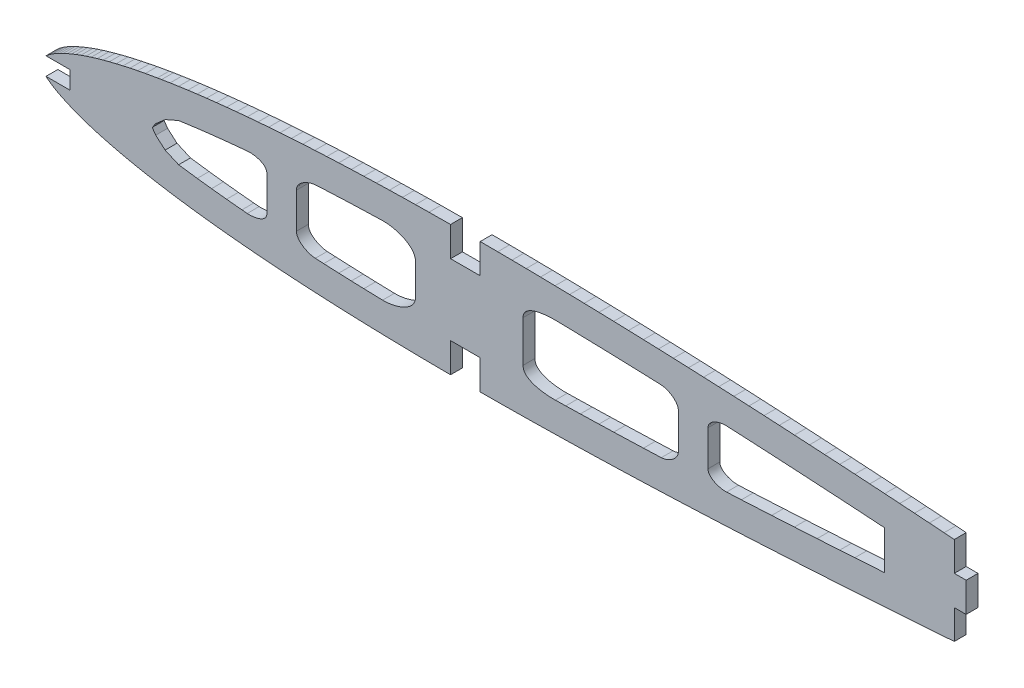
SolidWorks part; units mm, degrees
ref_plane "前视基准面" through (0, 0, 0) normal (0, 0, 1) x (1, 0, 0)
ref_plane "上视基准面" through (0, 0, 0) normal (0, 1, 0) x (1, 0, 0)
ref_plane "右视基准面" through (0, 0, 0) normal (1, 0, 0) x (0, 0, -1)
sketch "Model" plane through (0, 0, 0) normal (0, 0, 1) x (1, 0, 0)
  line L0 (365.1559, -97.3973) -> (369.2164, -97.3973)
  line L1 (369.2164, -97.3973) -> (369.2164, -100.3973)
  line L2 (369.2164, -100.3973) -> (365.1559, -100.3973)
  line L3 (438.4064, -87.9083) -> (438.4104, -92.9083)
  line L4 (438.4104, -92.9083) -> (433.4104, -92.9143)
  line L5 (433.4104, -92.9143) -> (433.4064, -87.9143)
  line L6 (438.4064, -109.8863) -> (438.4124, -104.8863)
  line L7 (438.4124, -104.8863) -> (433.4124, -104.8803)
  line L8 (433.4124, -104.8803) -> (433.4064, -109.8803)
  line L9 (518.3903, -91.4457) -> (516.6664, -91.3183)
  line L10 (516.6664, -91.3183) -> (514.1714, -91.1393)
  line L11 (514.1714, -91.1393) -> (511.6764, -90.9633)
  line L12 (511.6764, -90.9633) -> (509.1804, -90.7903)
  line L13 (509.1804, -90.7903) -> (506.6554, -90.6183)
  line L14 (506.6554, -90.6183) -> (504.1314, -90.4503)
  line L15 (504.1314, -90.4503) -> (501.6054, -90.2873)
  line L16 (501.6054, -90.2873) -> (499.0594, -90.1283)
  line L17 (499.0594, -90.1283) -> (496.5144, -89.9743)
  line L18 (496.5144, -89.9743) -> (493.9684, -89.8233)
  line L19 (493.9684, -89.8233) -> (491.4134, -89.6743)
  line L20 (491.4134, -89.6743) -> (488.8584, -89.5283)
  line L21 (488.8584, -89.5283) -> (486.3034, -89.3863)
  line L22 (486.3034, -89.3863) -> (483.7484, -89.2513)
  line L23 (483.7484, -89.2513) -> (481.1944, -89.1213)
  line L24 (481.1944, -89.1213) -> (478.6384, -88.9983)
  line L25 (478.6384, -88.9983) -> (476.0924, -88.8813)
  line L26 (476.0924, -88.8813) -> (473.5474, -88.7693)
  line L27 (473.5474, -88.7693) -> (471.0014, -88.6633)
  line L28 (471.0014, -88.6633) -> (468.4764, -88.5643)
  line L29 (468.4764, -88.5643) -> (465.9524, -88.4703)
  line L30 (465.9524, -88.4703) -> (463.4264, -88.3833)
  line L31 (463.4264, -88.3833) -> (460.9314, -88.3033)
  line L32 (460.9314, -88.3033) -> (458.4364, -88.2303)
  line L33 (458.4364, -88.2303) -> (455.9404, -88.1633)
  line L34 (455.9404, -88.1633) -> (453.4854, -88.1043)
  line L35 (453.4854, -88.1043) -> (451.0314, -88.0523)
  line L36 (451.0314, -88.0523) -> (448.5764, -88.0073)
  line L37 (448.5764, -88.0073) -> (446.1704, -87.9703)
  line L38 (446.1704, -87.9703) -> (443.7664, -87.9423)
  line L39 (443.7664, -87.9423) -> (441.3604, -87.9213)
  line L40 (441.3604, -87.9213) -> (438.4064, -87.9083)
  line L41 (383.9404, -91.2373) -> (379.0174, -92.1113)
  line L42 (387.5324, -95.6683) -> (390.6644, -95.2413)
  line L43 (390.6644, -95.2413) -> (393.0784, -94.9513)
  line L44 (393.0784, -94.9513) -> (395.6144, -94.6733)
  line L45 (395.6144, -94.6733) -> (398.2099, -94.4193)
  line L46 (398.2099, -94.4193) -> (399.256, -94.3267)
  line L47 (410.7501, -93.5242) -> (412.0079, -93.4582)
  line L48 (412.0079, -93.4582) -> (414.9885, -93.3234)
  line L49 (414.9885, -93.3234) -> (416.6574, -93.2563)
  line L50 (416.6574, -93.2563) -> (418.7714, -93.1823)
  line L51 (418.7714, -93.1823) -> (421.9864, -93.0883)
  line L52 (421.9343, -104.7047) -> (418.7714, -104.6123)
  line L53 (418.7714, -104.6123) -> (416.6574, -104.5383)
  line L54 (416.6574, -104.5383) -> (414.5434, -104.4533)
  line L55 (414.5434, -104.4533) -> (412.0079, -104.3363)
  line L56 (412.0079, -104.3363) -> (410.5909, -104.2619)
  line L57 (399.1076, -103.4547) -> (398.2099, -103.3753)
  line L58 (398.2099, -103.3753) -> (395.6144, -103.1213)
  line L59 (395.6144, -103.1213) -> (393.0784, -102.8433)
  line L60 (393.0784, -102.8433) -> (390.6644, -102.5533)
  line L61 (390.6644, -102.5533) -> (387.5324, -102.1263)
  line L62 (451.3201, -93.0601) -> (452.8362, -93.0905)
  line L63 (452.8362, -93.0905) -> (455.2997, -93.1479)
  line L64 (455.2997, -93.1479) -> (458.4364, -93.2303)
  line L65 (458.4364, -93.2303) -> (460.9314, -93.3033)
  line L66 (460.9314, -93.3033) -> (465.9524, -93.4703)
  line L67 (465.9524, -93.4703) -> (468.8582, -93.5804)
  line L68 (479.9184, -94.063) -> (482.4714, -94.1863)
  line L69 (482.4714, -94.1863) -> (487.5809, -94.4573)
  line L70 (487.5809, -94.4573) -> (491.4134, -94.6743)
  line L71 (491.4134, -94.6743) -> (495.2414, -94.8988)
  line L72 (495.2414, -94.8988) -> (499.0594, -95.1283)
  line L73 (499.0594, -95.1283) -> (501.6054, -95.2873)
  line L74 (501.6054, -95.2873) -> (506.6554, -95.6183)
  line L75 (506.6554, -102.1763) -> (501.6054, -102.5073)
  line L76 (501.6054, -102.5073) -> (499.0594, -102.6663)
  line L77 (499.0594, -102.6663) -> (495.2414, -102.8958)
  line L78 (495.2414, -102.8958) -> (491.4134, -103.1203)
  line L79 (491.4134, -103.1203) -> (487.5809, -103.3373)
  line L80 (487.5809, -103.3373) -> (482.4714, -103.6083)
  line L81 (482.4714, -103.6083) -> (479.9656, -103.7292)
  line L82 (468.9559, -104.2104) -> (465.9524, -104.3243)
  line L83 (465.9524, -104.3243) -> (460.9314, -104.4913)
  line L84 (460.9314, -104.4913) -> (458.4364, -104.5643)
  line L85 (458.4364, -104.5643) -> (455.2997, -104.6467)
  line L86 (455.2997, -104.6467) -> (452.8362, -104.704)
  line L87 (452.8362, -104.704) -> (451.0861, -104.7391)
  line L88 (387.5324, -95.6683) -> (385.2532, -96.6702)
  line L89 (385.2532, -96.6702) -> (383.6712, -98.0522)
  line L90 (383.6712, -98.0522) -> (383.078, -98.8973)
  line L91 (387.5324, -102.1263) -> (385.2532, -101.1243)
  line L92 (385.2532, -101.1243) -> (383.6712, -99.7423)
  line L93 (383.6712, -99.7423) -> (383.078, -98.8973)
  line L94 (427.4864, -96.2466) -> (427.4864, -101.548)
  line L95 (445.635, -95.4141) -> (445.635, -102.3805)
  line L96 (407.4071, -95.8973) -> (407.4071, -101.8973)
  line L97 (402.4071, -101.8973) -> (402.4071, -95.8973)
  line L98 (476.8379, -95.8973) -> (476.8379, -101.8973)
  line L99 (471.8379, -101.8973) -> (471.8379, -95.8973)
  line L100 (520.3903, -98.8973) -> (520.3903, -96.3973)
  line L101 (520.3903, -98.8973) -> (520.3903, -101.3973)
  line L102 (520.3903, -96.3973) -> (518.3903, -96.3973)
  line L103 (520.3903, -101.3973) -> (518.3903, -101.3973)
  line L104 (518.3903, -96.3973) -> (518.3903, -91.444)
  line L105 (518.3903, -101.3973) -> (518.3903, -106.3499)
  line L106 (506.6554, -95.6183) -> (506.6554, -102.1763)
  line L107 (433.4064, -87.9143) -> (429.7654, -87.9423)
  line L108 (429.7654, -87.9423) -> (427.4864, -87.9723)
  line L109 (427.4864, -87.9723) -> (425.2864, -88.0113)
  line L110 (425.2864, -88.0113) -> (423.0864, -88.0593)
  line L111 (423.0864, -88.0593) -> (420.8864, -88.1173)
  line L112 (420.8864, -88.1173) -> (418.7714, -88.1823)
  line L113 (418.7714, -88.1823) -> (416.6574, -88.2563)
  line L114 (416.6574, -88.2563) -> (414.5434, -88.3413)
  line L115 (414.5434, -88.3413) -> (412.5224, -88.4323)
  line L116 (412.5224, -88.4323) -> (410.5024, -88.5343)
  line L117 (410.5024, -88.5343) -> (408.4824, -88.6463)
  line L118 (408.4824, -88.6463) -> (406.5644, -88.7643)
  line L119 (406.5644, -88.7643) -> (404.6474, -88.8943)
  line L120 (404.6474, -88.8943) -> (402.7304, -89.0353)
  line L121 (402.7304, -89.0353) -> (400.9214, -89.1793)
  line L122 (400.9214, -89.1793) -> (399.1134, -89.3353)
  line L123 (399.1134, -89.3353) -> (397.3064, -89.5033)
  line L124 (397.3064, -89.5033) -> (395.6144, -89.6733)
  line L125 (395.6144, -89.6733) -> (393.9234, -89.8543)
  line L126 (393.9234, -89.8543) -> (392.2334, -90.0483)
  line L127 (392.2334, -90.0483) -> (390.6644, -90.2413)
  line L128 (390.6644, -90.2413) -> (389.0974, -90.4483)
  line L129 (389.0974, -90.4483) -> (387.5324, -90.6683)
  line L130 (387.5324, -90.6683) -> (386.0934, -90.8853)
  line L131 (386.0934, -90.8853) -> (384.6574, -91.1153)
  line L132 (384.6574, -91.1153) -> (383.2234, -91.3593)
  line L133 (383.2234, -91.3593) -> (381.9184, -91.5963)
  line L134 (381.9184, -91.5963) -> (380.6174, -91.8473)
  line L135 (380.6174, -91.8473) -> (379.3184, -92.1143)
  line L136 (379.3184, -92.1143) -> (378.1544, -92.3693)
  line L137 (378.1544, -92.3693) -> (376.9934, -92.6403)
  line L138 (376.9934, -92.6403) -> (375.8364, -92.9273)
  line L139 (375.8364, -92.9273) -> (374.8164, -93.1963)
  line L140 (374.8164, -93.1963) -> (373.8004, -93.4803)
  line L141 (373.8004, -93.4803) -> (372.7894, -93.7843)
  line L142 (372.7894, -93.7843) -> (371.9164, -94.0643)
  line L143 (371.9164, -94.0643) -> (371.0504, -94.3633)
  line L144 (371.0504, -94.3633) -> (370.1914, -94.6823)
  line L145 (370.1914, -94.6823) -> (369.4714, -94.9713)
  line L146 (369.4714, -94.9713) -> (368.7584, -95.2773)
  line L147 (368.7584, -95.2773) -> (368.0524, -95.6003)
  line L148 (368.0524, -95.6003) -> (367.4844, -95.8783)
  line L149 (367.4844, -95.8783) -> (366.9254, -96.1743)
  line L150 (366.9254, -96.1743) -> (366.3794, -96.4943)
  line L151 (366.3794, -96.4943) -> (365.9634, -96.7673)
  line L152 (365.9634, -96.7673) -> (365.5614, -97.0603)
  line L153 (365.5614, -97.0603) -> (365.1784, -97.3763)
  line L154 (365.1784, -97.3763) -> (365.1559, -97.3973)
  line L155 (438.4064, -109.8863) -> (441.3604, -109.8723)
  line L156 (441.3604, -109.8723) -> (443.7664, -109.8523)
  line L157 (443.7664, -109.8523) -> (446.1704, -109.8233)
  line L158 (446.1704, -109.8233) -> (448.5764, -109.7873)
  line L159 (448.5764, -109.7873) -> (451.0314, -109.7423)
  line L160 (451.0314, -109.7423) -> (453.4854, -109.6903)
  line L161 (453.4854, -109.6903) -> (455.9404, -109.6313)
  line L162 (455.9404, -109.6313) -> (458.4364, -109.5643)
  line L163 (458.4364, -109.5643) -> (460.9314, -109.4913)
  line L164 (460.9314, -109.4913) -> (463.4264, -109.4113)
  line L165 (463.4264, -109.4113) -> (465.9524, -109.3233)
  line L166 (465.9524, -109.3233) -> (468.4764, -109.2303)
  line L167 (468.4764, -109.2303) -> (471.0014, -109.1303)
  line L168 (471.0014, -109.1303) -> (473.5474, -109.0243)
  line L169 (473.5474, -109.0243) -> (476.0924, -108.9133)
  line L170 (476.0924, -108.9133) -> (478.6384, -108.7963)
  line L171 (478.6384, -108.7963) -> (481.1944, -108.6723)
  line L172 (481.1944, -108.6723) -> (483.7484, -108.5433)
  line L173 (483.7484, -108.5433) -> (486.3034, -108.4073)
  line L174 (486.3034, -108.4073) -> (488.8584, -108.2663)
  line L175 (488.8584, -108.2663) -> (491.4134, -108.1203)
  line L176 (491.4134, -108.1203) -> (493.9684, -107.9703)
  line L177 (493.9684, -107.9703) -> (496.5144, -107.8193)
  line L178 (496.5144, -107.8193) -> (499.0594, -107.6653)
  line L179 (499.0594, -107.6653) -> (501.6054, -107.5063)
  line L180 (501.6054, -107.5063) -> (504.1314, -107.3433)
  line L181 (504.1314, -107.3433) -> (506.6554, -107.1753)
  line L182 (506.6554, -107.1753) -> (509.1804, -107.0033)
  line L183 (509.1804, -107.0033) -> (511.6764, -106.8313)
  line L184 (511.6764, -106.8313) -> (514.1714, -106.6553)
  line L185 (514.1714, -106.6553) -> (516.6664, -106.4763)
  line L186 (516.6664, -106.4763) -> (518.3903, -106.3499)
  line L187 (365.1559, -100.3973) -> (365.1784, -100.4183)
  line L188 (365.1784, -100.4183) -> (365.5614, -100.7343)
  line L189 (365.5614, -100.7343) -> (365.9634, -101.0273)
  line L190 (365.9634, -101.0273) -> (366.3794, -101.2993)
  line L191 (366.3794, -101.2993) -> (366.9254, -101.6203)
  line L192 (366.9254, -101.6203) -> (367.4844, -101.9153)
  line L193 (367.4844, -101.9153) -> (368.0524, -102.1933)
  line L194 (368.0524, -102.1933) -> (368.7584, -102.5173)
  line L195 (368.7584, -102.5173) -> (369.4714, -102.8233)
  line L196 (369.4714, -102.8233) -> (370.1914, -103.1113)
  line L197 (370.1914, -103.1113) -> (371.0504, -103.4313)
  line L198 (371.0504, -103.4313) -> (371.9164, -103.7293)
  line L199 (371.9164, -103.7293) -> (372.7894, -104.0103)
  line L200 (372.7894, -104.0103) -> (373.8004, -104.3133)
  line L201 (373.8004, -104.3133) -> (374.8164, -104.5983)
  line L202 (374.8164, -104.5983) -> (375.8364, -104.8673)
  line L203 (375.8364, -104.8673) -> (376.9934, -105.1543)
  line L204 (376.9934, -105.1543) -> (378.1544, -105.4253)
  line L205 (378.1544, -105.4253) -> (379.3184, -105.6803)
  line L206 (379.3184, -105.6803) -> (380.6174, -105.9473)
  line L207 (380.6174, -105.9473) -> (381.9184, -106.1983)
  line L208 (381.9184, -106.1983) -> (383.2234, -106.4343)
  line L209 (383.2234, -106.4343) -> (384.6574, -106.6793)
  line L210 (384.6574, -106.6793) -> (386.0934, -106.9093)
  line L211 (386.0934, -106.9093) -> (387.5324, -107.1253)
  line L212 (387.5324, -107.1253) -> (389.0974, -107.3463)
  line L213 (389.0974, -107.3463) -> (390.6644, -107.5523)
  line L214 (390.6644, -107.5523) -> (392.2334, -107.7463)
  line L215 (392.2334, -107.7463) -> (393.9234, -107.9403)
  line L216 (393.9234, -107.9403) -> (395.6144, -108.1213)
  line L217 (395.6144, -108.1213) -> (397.3064, -108.2903)
  line L218 (397.3064, -108.2903) -> (399.1134, -108.4583)
  line L219 (399.1134, -108.4583) -> (400.9214, -108.6143)
  line L220 (400.9214, -108.6143) -> (402.7304, -108.7593)
  line L221 (402.7304, -108.7593) -> (404.6474, -108.9003)
  line L222 (404.6474, -108.9003) -> (406.5644, -109.0293)
  line L223 (406.5644, -109.0293) -> (408.4824, -109.1473)
  line L224 (408.4824, -109.1473) -> (410.5024, -109.2603)
  line L225 (410.5024, -109.2603) -> (412.5224, -109.3613)
  line L226 (412.5224, -109.3613) -> (414.5434, -109.4523)
  line L227 (414.5434, -109.4523) -> (416.6574, -109.5373)
  line L228 (416.6574, -109.5373) -> (418.7714, -109.6123)
  line L229 (418.7714, -109.6123) -> (420.8864, -109.6773)
  line L230 (420.8864, -109.6773) -> (423.0864, -109.7353)
  line L231 (423.0864, -109.7353) -> (425.2864, -109.7833)
  line L232 (425.2864, -109.7833) -> (427.4864, -109.8213)
  line L233 (427.4864, -109.8213) -> (429.7654, -109.8513)
  line L234 (429.7654, -109.8513) -> (433.4064, -109.8803)
  spline S0 degree 3 poles (421.9864, -93.0883) (424.0996, -93.0265) (427.4864, -94.1325) (427.4864, -96.2466) knots 0 0 0 0 6.342328 6.342328 6.342328 6.342328
  spline S1 degree 3 poles (421.9343, -104.7047) (424.0623, -104.767) (427.4864, -103.6769) (427.4864, -101.548) knots 0 0 0 0 6.386793 6.386793 6.386793 6.386793
  spline S2 degree 3 poles (445.635, -95.4141) (445.635, -93.363) (449.2694, -93.019) (451.3201, -93.0601) knots 0 0 0 0 6.153175 6.153175 6.153175 6.153175
  spline S3 degree 3 poles (445.635, -102.3805) (445.635, -104.3603) (449.1067, -104.7787) (451.0861, -104.7391) knots 0 0 0 0 5.93954 5.93954 5.93954 5.93954
  spline S4 degree 3 poles (399.256, -94.3267) (400.425, -94.2232) (402.4071, -94.7237) (402.4071, -95.8973) knots 0 0 0 0 3.52078 3.52078 3.52078 3.52078
  spline S5 degree 3 poles (399.1076, -103.4547) (400.319, -103.5619) (402.4071, -103.1135) (402.4071, -101.8973) knots 0 0 0 0 3.648605 3.648605 3.648605 3.648605
  spline S6 degree 3 poles (410.7501, -93.5242) (409.3855, -93.5959) (407.4071, -94.5307) (407.4071, -95.8973) knots 0 0 0 0 4.09968 4.09968 4.09968 4.09968
  spline S7 degree 3 poles (410.5909, -104.2619) (409.2708, -104.1926) (407.4071, -103.2192) (407.4071, -101.8973) knots 0 0 0 0 3.965934 3.965934 3.965934 3.965934
  spline S8 degree 3 poles (468.8582, -93.5804) (470.1154, -93.628) (471.8379, -94.6391) (471.8379, -95.8973) knots 0 0 0 0 3.774504 3.774504 3.774504 3.774504
  spline S9 degree 3 poles (468.9559, -104.2104) (470.1869, -104.1638) (471.8379, -103.1291) (471.8379, -101.8973) knots 0 0 0 0 3.695535 3.695535 3.695535 3.695535
  spline S10 degree 3 poles (479.9184, -94.063) (478.7247, -94.0054) (476.8379, -94.7022) (476.8379, -95.8973) knots 0 0 0 0 3.585193 3.585193 3.585193 3.585193
  spline S11 degree 3 poles (479.9656, -103.7292) (478.7588, -103.7875) (476.8379, -103.1055) (476.8379, -101.8973) knots 0 0 0 0 3.624712 3.624712 3.624712 3.624712
extrude "凸台-拉伸2" add sketch "Model" along normal blind 2 contours L233 L234 L8 L7 L6 L155 L156 L157 L158 L159 L160 L161 L162 L163 L164 L165 L166 L167 L168 L169 L170 L171 L172 L173 L174 L175 L176 L177 L178 L179 L180 L181 L182 L183 L184 L185 L186 L105 L103 L101 L100 L102 L104 L9 L10 L11 L12 L13 L14 L15 L16 region at (444.1852, -98.8968, 0)
